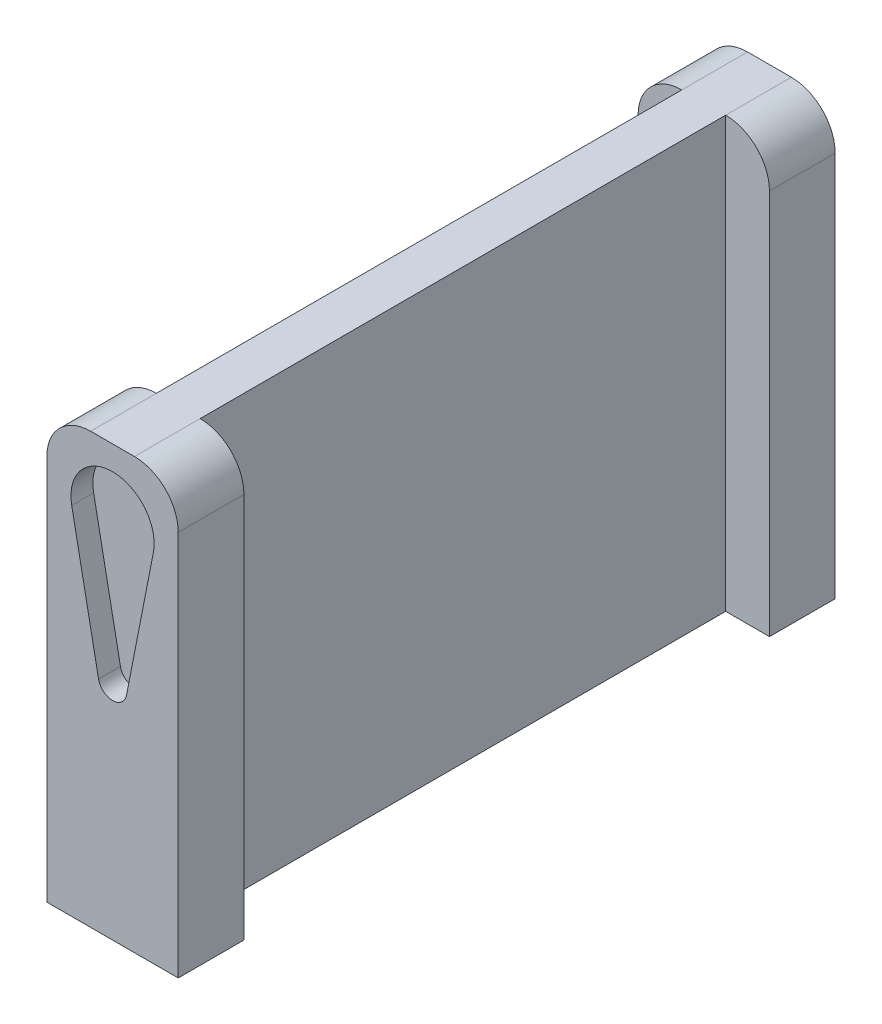
SolidWorks part; units mm, degrees
ref_plane "Front Plane" through (0, 0, 0) normal (0, 0, 1) x (1, 0, 0)
ref_plane "Top Plane" through (0, 0, 0) normal (0, 1, 0) x (1, 0, 0)
ref_plane "Right Plane" through (0, 0, 0) normal (1, 0, 0) x (0, 0, -1)
sketch "Sketch1" plane through (0, 0, 0) normal (0, 0, 1) x (1, 0, 0)
  line L0 (0, 0) -> (0, -13) construction
  line L1 (-0.9813, -13.1923) -> (-3.4347, -0.6731) construction
  line L2 (0.9813, -13.1923) -> (3.4347, -0.6731) construction
  circle A0 centre (0, 0) radius 3.5 construction
  circle A1 centre (0, -13) radius 1 construction
  point P7 (0, -14)
  point P10 (0, 3.5)
  point P11 (0, 0)
  dimension "D1" = 7
  dimension "D3" = 2
  dimension "D2" = 13
ref_plane "Plane2" through (0, 6, 0) normal (0, 1, 0) x (1, 0, 0)
sketch "Sketch4" plane through (0, 6, 0) normal (0, 1, 0) x (1, 0, 0)
  line L0 (-6, 30) -> (6, 30)
  line L1 (6, 30) -> (6, 24)
  line L2 (6, 24) -> (2, 24)
  line L3 (2, 24) -> (2, -24)
  line L4 (2, -24) -> (6, -24)
  line L5 (6, -24) -> (6, -30)
  line L6 (6, -30) -> (-6, -30)
  line L7 (-6, -30) -> (-6, -24)
  line L8 (-6, -24) -> (-2, -24)
  line L9 (-2, -24) -> (-2, 24)
  line L10 (-2, 24) -> (-6, 24)
  line L11 (-6, 24) -> (-6, 30)
  point P12 (-2, 0)
  point P14 (0, 30)
  dimension "D1" = 6
  dimension "D2" = 60
  dimension "D3" = 6
  dimension "D4" = 4
extrude "Boss-Extrude2" add sketch "Sketch4" against normal blind 39.25
sketch "Sketch5" plane through (0, 0, 30) normal (0, 0, 1) x (1, 0, 0)
  line L0 (3.7291, -0.7308) -> (1.2757, -13.25)
  line L9 (-3.7291, -0.7308) -> (-1.2757, -13.25)
  arc A9 (3.7291, -0.7308) -> (-3.7291, -0.7308) centre (0, 0) ccw
  circle A10 centre (0, 0) radius 3.5 construction
  arc A11 (-1.2757, -13.25) -> (1.2757, -13.25) centre (0, -13) ccw
  circle A12 centre (0, -13) radius 1 construction
  dimension "D1" = 0.3
  dimension "D2" = 0.3
extrude "Cut-Extrude1" cut sketch "Sketch5" against normal blind 2
mirror "Mirror1" about plane through (0, 0, 0) normal (0, 0, 1) of "Cut-Extrude1"
fillet "Fillet1" radius 4 4 edges at (-6, 6, -27) (6, 6, -27) (6, 6, 27) (-6, 6, 27)
